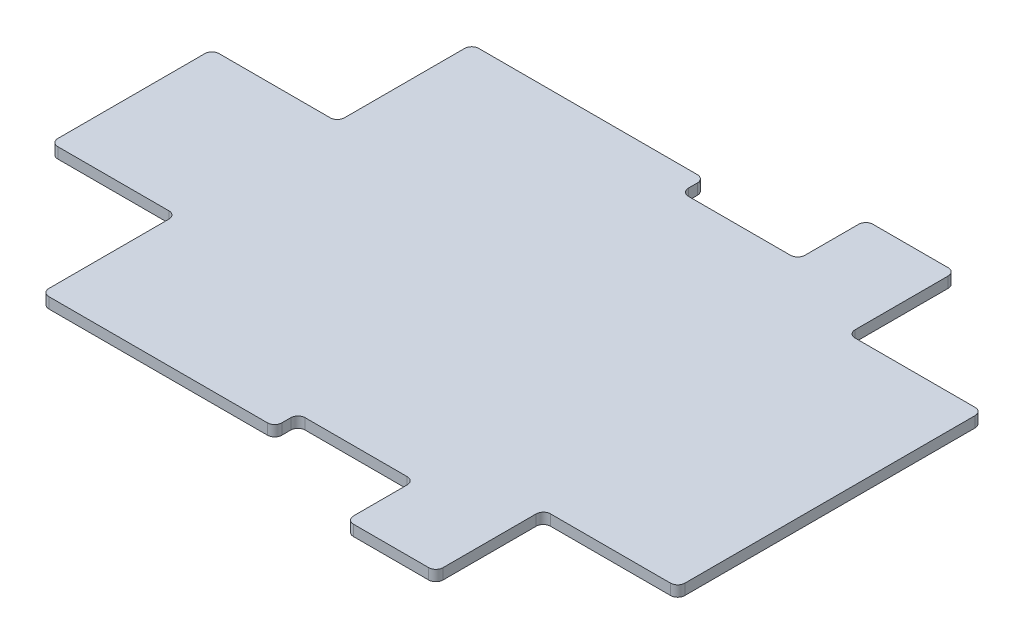
SolidWorks part; units mm, degrees
material "Aleación 1060"
ref_plane "Alzado" through (0, 0, 0) normal (0, 0, 1) x (1, 0, 0)
ref_plane "Planta" through (0, 0, 0) normal (0, 1, 0) x (1, 0, 0)
ref_plane "Vista lateral" through (0, 0, 0) normal (1, 0, 0) x (0, 0, -1)
sketch "Croquis1" plane through (0, 0, 0) normal (0, 1, 0) x (1, 0, 0)
  line L0 (0, 0) -> (-390, 0)
  line L1 (-390, 0) -> (-390, 45)
  line L2 (-390, 45) -> (-320, 45)
  line L3 (-320, 45) -> (-320, 120)
  line L4 (-320, 120) -> (-190, 120)
  line L5 (-190, 120) -> (-190, 107)
  line L6 (-190, 107) -> (-125, 107)
  line L7 (-125, 107) -> (-125, 145)
  line L8 (-125, 145) -> (-75, 145)
  line L9 (-75, 145) -> (-75, 85)
  line L10 (0, 0) -> (0, 85)
  line L11 (0, 85) -> (-75, 85)
  dimension "D1" = 390
  dimension "D2" = 45
  dimension "D3" = 75
  dimension "D4" = 120
  dimension "D5" = 130
  dimension "D6" = 13
  dimension "D7" = 50
  dimension "D8" = 85
  dimension "D9" = 65
  dimension "D10" = 60
extrude "Saliente-Extruir1" add sketch "Croquis1" along normal blind 6
mirror "Simetría1" about plane through (0, 6, 0) normal (0, 0, -1) of "Saliente-Extruir1"
fillet "Redondeo1" radius 4 20 edges at (-390, 3, -45) (-320, 3, -45) (-320, 3, -120) (-190, 3, -120) (-190, 3, -107) (-125, 3, -107) (-125, 3, -145) (-75, 3, -85) (-75, 3, -145) (0, 3, -85) (0, 3, 85) (-75, 3, 85) (-75, 3, 145) (-125, 3, 145) (-125, 3, 107) (-190, 3, 107) (-190, 3, 120) (-320, 3, 120) (-320, 3, 45) (-390, 3, 45)
sketch "Croquis2" plane through (0, 6, 0) normal (0, 1, 0) x (1, 0, 0)
  line L0 (-390, 0) -> (0, 0) construction
  line L1 (-390, 41) -> (-390, -41) construction
  line L2 (0, -81) -> (0, 81) construction
  line L3 (-214.7209, -131) -> (31.1095, -131) construction
  line L4 (-214.0485, -154) -> (44.3152, -154) construction
  line L5 (-79, -145) -> (-121, -145) construction
  line L6 (-44, -177) -> (-156, -177)
  line L7 (-44, -177) -> (-44, -131)
  line L8 (-44, -131) -> (-156, -131)
  line L9 (-156, -177) -> (-156, -131)
  line L10 (-44, -177) -> (-156, -131) construction
  line L11 (-44, -131) -> (-156, -177) construction
  line L12 (-156, 154) -> (-44, 154) construction
  line L13 (-374, -177) -> (-486, -177)
  line L14 (-374, -177) -> (-374, -131)
  line L15 (-374, -131) -> (-486, -131)
  line L16 (-486, -177) -> (-486, -131)
  line L17 (-374, -177) -> (-486, -131) construction
  line L18 (-374, -131) -> (-486, -177) construction
  line L19 (-44, 177) -> (-156, 177)
  line L20 (-44, 177) -> (-44, 131)
  line L21 (-44, 131) -> (-156, 131)
  line L22 (-156, 177) -> (-156, 131)
  line L23 (-374, 131) -> (-486, 177) construction
  line L24 (-374, 177) -> (-486, 131) construction
  line L25 (-486, 177) -> (-486, 131)
  line L26 (-374, 131) -> (-486, 131)
  line L27 (-374, 177) -> (-374, 131)
  line L28 (-374, 177) -> (-486, 177)
  line L29 (-430, -154) -> (-430, 154) construction
  point P10 (-100, -154)
  point P17 (-100, -145)
  point P20 (-430, -154)
  point P33 (-430, 154)
  dimension "D1" = 131
  dimension "D2" = 154
  dimension "D3" = 46
  dimension "D4" = 112
  dimension "D5" = 330
sketch "Croquis3" plane through (0, 6, 0) normal (0, 1, 0) x (1, 0, 0)
  line L0 (-100, -145) -> (-100, 145) construction
  line L1 (-79, -145) -> (-121, -145) construction
  line L2 (-79, 145) -> (-121, 145) construction
  line L3 (-161.61, 16.8885) -> (-161.61, -25.475) construction
  line L4 (-232.2, 27.5722) -> (-232.2, -25.475) construction
  dimension "D1" = 132.2
  dimension "D2" = 61.61
ref_plane "Plano1" [suppressed] through (-430, 0, 0) normal (1, 0, 0) x (0, 0, -1)
